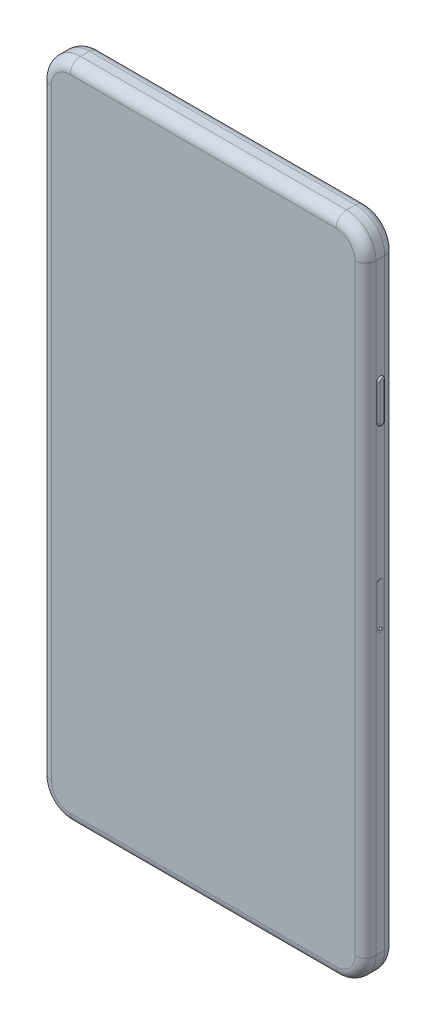
SolidWorks part; units mm, degrees
material "Cast Alloy Steel"
ref_plane "Front Plane" through (0, 0, 0) normal (0, 0, 1) x (1, 0, 0)
ref_plane "Top Plane" through (0, 0, 0) normal (0, 1, 0) x (1, 0, 0)
ref_plane "Right Plane" through (0, 0, 0) normal (1, 0, 0) x (0, 0, -1)
sketch "Sketch1" plane through (0, 0, 0) normal (0, 0, 1) x (1, 0, 0)
  line L0 (-36.2, 71.25) -> (-36.2, -71.25)
  line L1 (-31.7, 78.75) -> (31.7, 78.75)
  line L2 (-38.7, 71.75) -> (-38.7, -71.75)
  line L3 (-31.7, -78.75) -> (31.7, -78.75)
  line L4 (38.7, 71.75) -> (38.7, -71.75)
  line L5 (-38.7, 78.75) -> (38.7, -78.75) construction
  line L6 (-38.7, -78.75) -> (38.7, 78.75) construction
  line L7 (-31.2, -76.25) -> (31.2, -76.25)
  line L8 (36.2, 71.25) -> (36.2, -71.25)
  line L9 (-31.2, 76.25) -> (-22.375, 76.25)
  line L10 (-38.7, 78.75) -> (38.7, 78.75) construction
  line L11 (38.7, 78.75) -> (38.7, -78.75) construction
  line L12 (-38.7, 78.75) -> (-38.7, -78.75) construction
  line L13 (-38.7, -78.75) -> (38.7, -78.75) construction
  line L14 (36.2, 76.25) -> (36.2, -76.25) construction
  line L15 (-36.2, 76.25) -> (36.2, 76.25) construction
  line L16 (-36.2, -76.25) -> (36.2, -76.25) construction
  line L17 (-36.2, 76.25) -> (-36.2, -76.25) construction
  line L18 (22.375, 76.25) -> (31.2, 76.25)
  line L20 (-21.875, 75.75) -> (-21.875, 74.4325)
  line L21 (-18.875, 71.4325) -> (18.875, 71.4325)
  line L22 (21.875, 75.75) -> (21.875, 74.4325)
  arc A0 (31.7, 78.75) -> (38.7, 71.75) centre (31.7, 71.75) cw
  arc A1 (-38.7, -71.75) -> (-31.7, -78.75) centre (-31.7, -71.75) ccw
  arc A2 (-31.7, 78.75) -> (-38.7, 71.75) centre (-31.7, 71.75) ccw
  arc A3 (31.7, -78.75) -> (38.7, -71.75) centre (31.7, -71.75) ccw
  arc A4 (36.2, 71.25) -> (31.2, 76.25) centre (31.2, 71.25) ccw
  arc A5 (31.2, -76.25) -> (36.2, -71.25) centre (31.2, -71.25) ccw
  arc A6 (-36.2, -71.25) -> (-31.2, -76.25) centre (-31.2, -71.25) ccw
  arc A7 (-36.2, 71.25) -> (-31.2, 76.25) centre (-31.2, 71.25) cw
  arc A8 (18.875, 71.4325) -> (21.875, 74.4325) centre (18.875, 74.4325) ccw
  arc A9 (-21.875, 74.4325) -> (-18.875, 71.4325) centre (-18.875, 74.4325) ccw
  arc A10 (21.875, 75.75) -> (22.375, 76.25) centre (22.375, 75.75) cw
  arc A11 (-21.875, 75.75) -> (-22.375, 76.25) centre (-22.375, 75.75) ccw
  point P0 (0, 0)
  point P34 (0, 76.25)
  point P45 (21.875, 76.25)
  dimension "D4" = 7
  dimension "D5" = 5
  dimension "D6" = 3
  dimension "D7" = 0.5
  dimension "D1" = 157.5
  dimension "D2" = 77.4
  dimension "D3" = 2.5
extrude "Boss-Extrude1" add sketch "Sketch1" against normal blind 7.1 contours L2 A1 L3 A3 L4 A0 L1 A2
extrude "Cut-Extrude1" cut sketch "Sketch1<3>" against normal blind 0.1 contours L0 A6 L7 A5 L8 A4 L18 A10 L22 A8 L21 A9 L20 A11 L9 A7
sketch "Sketch1<3>" plane through (0, 0, 0) normal (0, 0, 1) x (1, 0, 0) same geometry as "Sketch1"
fillet "Fillet1" radius 2.5 16 edges at (-36.6497, 76.6997, 0) (0, 78.75, 0) (36.6497, 76.6997, 0) (38.7, 0, 0) (36.6497, -76.6997, 0) (0, -78.75, 0) (-36.6497, -76.6997, 0) (-38.7, 0, -7.1) (-36.6497, -76.6997, -7.1) (0, -78.75, -7.1) (36.6497, -76.6997, -7.1) (38.7, 0, -7.1) (36.6497, 76.6997, -7.1) (0, 78.75, -7.1) (-36.6497, 76.6997, -7.1) (-38.7, 0, 0)
sketch "Sketch2" plane through (0, 0, 0) normal (0, 0, 1) x (1, 0, 0)
  line L0 (0, 76.25) -> (0, 71.4325) construction
  line L1 (22.375, 76.25) -> (-22.375, 76.25) construction
  line L4 (-18.875, 71.4325) -> (18.875, 71.4325) construction
  line L5 (-4.3825, 73.8413) -> (4.3825, 73.8413) construction
  line L6 (-4.3825, 74.5173) -> (4.3825, 74.5173)
  line L7 (-4.3825, 73.1652) -> (4.3825, 73.1652)
  arc A3 (-4.3825, 74.5173) -> (-4.3825, 73.1652) centre (-4.3825, 73.8413) ccw
  arc A4 (4.3825, 73.1652) -> (4.3825, 74.5173) centre (4.3825, 73.8413) ccw
  circle A5 centre (7.3325, 73.8412) radius 0.676
  point P9 (0, 73.8412)
  dimension "D1" = 8.765
  dimension "D2" = 2.95
extrude "Cut-Extrude3" cut sketch "Sketch2" against normal blind 0.3
sketch "Sketch3" plane through (0, 0, -7.1) normal (0, 0, -1) x (-1, 0, 0)
  line L0 (-29.2, 69.25) -> (-29.2, 56.75) construction
  line L1 (-25.6, 69.25) -> (-25.6, 56.75)
  line L2 (-32.8, 69.25) -> (-32.8, 56.75)
  line L3 (31.7, 76.25) -> (-31.7, 76.25) construction
  line L4 (-36.2, 71.75) -> (-36.2, -71.75) construction
  arc A0 (-25.6, 69.25) -> (-32.8, 69.25) centre (-29.2, 69.25) ccw
  arc A1 (-32.8, 56.75) -> (-25.6, 56.75) centre (-29.2, 56.75) ccw
  circle A2 centre (-29.2, 63) radius 1.75
  circle A3 centre (-29.2, 69.25) radius 1.7
  circle A4 centre (-29.2, 56.75) radius 1.7
  point P2 (-29.2, 63)
  dimension "D4" = 3.6
  dimension "D1" = 12.5
  dimension "D2" = 7
  dimension "D3" = 7
sketch "Sketch4" plane through (38.7, 0, 0) normal (1, 0, 0) x (0, 0, -1)
  line L0 (2.5, 46.5699) -> (4.6, 46.5699) construction
  line L1 (2.5, 71.75) -> (2.5, -71.75) construction
  line L2 (4.6, -71.75) -> (4.6, 71.75) construction
  line L3 (3.55, 46.5699) -> (3.55, 38.0699) construction
  line L4 (4.3849, 46.5699) -> (4.3849, 38.0699)
  line L5 (2.7151, 46.5699) -> (2.7151, 38.0699)
  arc A0 (4.3849, 46.5699) -> (2.7151, 46.5699) centre (3.55, 46.5699) ccw
  arc A1 (2.7151, 38.0699) -> (4.3849, 38.0699) centre (3.55, 38.0699) ccw
  point P8 (3.55, 42.3199)
  point P13 (3.55, 43.1405)
  point P14 (3.55, 49.1617)
  point P15 (3.55, 42.3768)
  point P16 (3.55, 38.0699)
  dimension "D1" = 8.5
extrude "Boss-Extrude3" add sketch "Sketch4" along normal blind 0.4
fillet "Fillet3" radius 0.4 4 edges at (39.1, 42.3199, -4.3849) (39.1, 37.235, -3.55) (39.1, 42.3199, -2.7151) (39.1, 47.4049, -3.55)
sketch "Sketch5" plane through (38.7, 0, 0) normal (1, 0, 0) x (0, 0, -1)
  line L0 (2.5, 0) -> (4.6, 0) construction
  line L1 (2.5, 71.75) -> (2.5, -71.75) construction
  line L2 (4.6, -71.75) -> (4.6, 71.75) construction
  line L3 (3.55, -4.75) -> (3.55, 4.75) construction
  line L4 (2.7431, -4.75) -> (2.7431, 4.75)
  line L5 (4.3569, -4.75) -> (4.3569, 4.75)
  arc A0 (2.7431, -4.75) -> (4.3569, -4.75) centre (3.55, -4.75) ccw
  arc A1 (4.3569, 4.75) -> (2.7431, 4.75) centre (3.55, 4.75) ccw
  circle A2 centre (3.55, -4.75) radius 0.35
  point P8 (3.55, 0)
  dimension "D2" = 0.7
  dimension "D1" = 9.5
extrude "Boss-Extrude4" add sketch "Sketch5" along normal blind 0.02
sketch "Sketch6" plane through (38.7, 0, 0) normal (1, 0, 0) x (0, 0, -1)
  circle A0 centre (3.55, -4.75) radius 0.35
extrude "Cut-Extrude4" cut sketch "Sketch6" against normal blind 1
sketch "Sketch7" plane through (-38.7, 0, 0) normal (-1, 0, 0) x (0, 0, 1)
  line L0 (-2.7151, 46.5699) -> (-2.7151, 38.0699) construction
  line L1 (-4.3849, 38.0699) -> (-4.3849, 46.5699) construction
  line L2 (-2.7151, 46.5699) -> (-2.7151, 38.0699)
  line L3 (-4.3849, 38.0699) -> (-4.3849, 46.5699)
  line L4 (-4.6, 36.0651) -> (-2.5, 36.0651) construction
  line L5 (-4.6, 71.75) -> (-4.6, -71.75) construction
  line L6 (-2.5, -71.75) -> (-2.5, 71.75) construction
  line L7 (-4.3849, 34.0603) -> (-4.3849, 25.5603)
  line L8 (-2.7151, 25.5603) -> (-2.7151, 34.0603)
  arc A0 (-4.3849, 38.0699) -> (-2.7151, 38.0699) centre (-3.55, 38.0699) ccw construction
  arc A1 (-2.7151, 46.5699) -> (-4.3849, 46.5699) centre (-3.55, 46.5699) ccw construction
  arc A2 (-4.3849, 38.0699) -> (-2.7151, 38.0699) centre (-3.55, 38.0699) ccw
  arc A3 (-2.7151, 46.5699) -> (-4.3849, 46.5699) centre (-3.55, 46.5699) ccw
  arc A4 (-2.7151, 25.5603) -> (-4.3849, 25.5603) centre (-3.55, 25.5603) cw
  arc A5 (-4.3849, 34.0603) -> (-2.7151, 34.0603) centre (-3.55, 34.0603) cw
extrude "Boss-Extrude5" add sketch "Sketch7" along normal blind 0.4
fillet "Fillet4" radius 0.4 8 edges at (-39.1, 29.8103, -4.3849) (-39.1, 34.8952, -3.55) (-39.1, 29.8103, -2.7151) (-39.1, 24.7253, -3.55) (-39.1, 42.3199, -2.7151) (-39.1, 37.235, -3.55) (-39.1, 42.3199, -4.3849) (-39.1, 47.4049, -3.55)
sketch "Sketch8" plane through (-38.7, 0, 0) normal (-1, 0, 0) x (0, 0, 1)
  line L0 (-4.6, 52.4032) -> (-2.5, 52.4032) construction
  line L1 (-4.6, 71.75) -> (-4.6, -71.75) construction
  line L2 (-2.5, -71.75) -> (-2.5, 71.75) construction
  line L3 (-3.55, 50.6532) -> (-3.55, 54.1532) construction
  line L4 (-4.1722, 50.6532) -> (-4.1722, 54.1532)
  line L5 (-2.9278, 50.6532) -> (-2.9278, 54.1532)
  arc A0 (-4.1722, 50.6532) -> (-2.9278, 50.6532) centre (-3.55, 50.6532) ccw
  arc A1 (-2.9278, 54.1532) -> (-4.1722, 54.1532) centre (-3.55, 54.1532) ccw
  point P8 (-3.55, 52.4032)
  dimension "D1" = 3.5
extrude "Cut-Extrude5" cut sketch "Sketch8" against normal blind 0.3
sketch "Sketch10" plane through (0, -78.75, 0) normal (0, -1, 0) x (1, 0, 0)
  line L0 (0, 0) -> (0, -7.1) construction
  line L1 (31.7, -7.1) -> (-31.7, -7.1) construction
  line L2 (2.4161, -4.3017) -> (2.8576, -3.8603)
  line L3 (-2.6454, -2.769) -> (2.6454, -2.769)
  line L4 (-2.8869, -2.969) -> (-2.8869, -3.7896)
  line L5 (-2.3454, -4.331) -> (2.3454, -4.331)
  line L6 (2.8869, -2.969) -> (2.8869, -3.7896)
  line L7 (-2.8869, -2.769) -> (2.8869, -4.331) construction
  line L8 (-2.8869, -4.331) -> (2.8869, -2.769) construction
  line L9 (-2.8576, -3.8603) -> (-2.4161, -4.3017)
  line L10 (-2.8869, -2.969) -> (-2.7161, -2.7983)
  line L11 (2.7161, -2.7983) -> (2.8869, -2.969)
  line L12 (-31.7, -4.6) -> (-31.7, -2.5) construction
  arc A0 (2.7161, -2.7983) -> (2.6454, -2.769) centre (2.6454, -2.869) ccw
  arc A1 (-2.7161, -2.7983) -> (-2.6454, -2.769) centre (-2.6454, -2.869) cw
  arc A2 (-2.4161, -4.3017) -> (-2.3454, -4.331) centre (-2.3454, -4.231) ccw
  arc A3 (-2.8576, -3.8603) -> (-2.8869, -3.7896) centre (-2.7869, -3.7896) cw
  arc A4 (2.8576, -3.8603) -> (2.8869, -3.7896) centre (2.7869, -3.7896) ccw
  arc A5 (2.4161, -4.3017) -> (2.3454, -4.331) centre (2.3454, -4.231) cw
  circle A6 centre (4.9115, -3.5328) radius 0.5
  circle A7 centre (-4.9115, -3.5328) radius 0.5
  circle A8 centre (29.251, -3.5328) radius 0.62
  circle A9 centre (27.251, -3.5328) radius 0.62
  circle A10 centre (25.251, -3.5328) radius 0.62
  circle A11 centre (23.251, -3.5328) radius 0.62
  circle A12 centre (21.251, -3.5328) radius 0.62
  circle A13 centre (19.251, -3.5328) radius 0.62
  circle A14 centre (17.251, -3.5328) radius 0.62
  circle A15 centre (15.251, -3.5328) radius 0.62
  circle A16 centre (-26.7, -3.4998) radius 0.62
  circle A21 centre (-24.7, -3.4998) radius 0.62
  circle A22 centre (-22.7, -3.4998) radius 0.62
  circle A23 centre (-20.7, -3.4998) radius 0.62
  circle A24 centre (-18.7, -3.4998) radius 0.62
  point P5 (0, -3.55)
  point P20 (2.6869, -2.769)
  point P23 (-2.6869, -2.769)
  point P26 (-2.3869, -4.331)
  point P29 (-2.8869, -3.831)
  point P32 (2.8869, -3.831)
  point P35 (2.3869, -4.331)
  dimension "D1" = 0.1
  dimension "D2" = 1
  dimension "D7" = 1.24
  dimension "D9" = 5
  dimension "D8" = 8
  dimension "D10" = 5
extrude "Cut-Extrude6" cut sketch "Sketch10" against normal blind 1 contours A16 | A21 | A22 | A23 | A24 | A5 L2 A4 L6 L11 A0 L3 A1 L10 L4 A3 L9 A2 L5 | A14 | A13 | A12 | A10 | A8 | A9 | A15 | A11 region at (0, -78.75, -3.5357) region at (29.251, -78.75, -3.5328) region at (27.251, -78.75, -3.5328) region at (25.251, -78.75, -3.5328) region at (21.251, -78.75, -3.5328) region at (19.251, -78.75, -3.5328) region at (17.251, -78.75, -3.5328) region at (-26.7, -78.75, -3.4998) region at (-24.7, -78.75, -3.4998) region at (-22.7, -78.75, -3.4998) region at (-20.7, -78.75, -3.4998) region at (-18.7, -78.75, -3.4998)
extrude "Cut-Extrude7" cut sketch "Sketch10<3>" against normal blind 0.3 contours A6 | A7 region at (4.9115, -78.75, -3.5328)
sketch "Sketch10<3>" plane through (0, -78.75, 0) normal (0, -1, 0) x (1, 0, 0) same geometry as "Sketch10"
sketch "Sketch12" plane through (0, 0, -0.1) normal (0, 0, 1) x (1, 0, 0)
  line L0 (-31.2, -76.25) -> (31.2, -76.25) construction
  line L1 (36.2, 71.25) -> (36.2, -71.25) construction
  line L2 (22.375, 76.25) -> (31.2, 76.25) construction
  line L3 (-36.2, 71.25) -> (-36.2, -71.25) construction
  line L4 (-31.2, 76.25) -> (-22.375, 76.25) construction
  line L5 (22.375, 76.25) -> (-22.375, 76.25) construction
  line L6 (-31.2, -76.25) -> (31.2, -76.25)
  line L7 (36.2, 71.25) -> (36.2, -71.25)
  line L8 (22.375, 76.25) -> (31.2, 76.25)
  line L9 (-36.2, 71.25) -> (-36.2, -71.25)
  line L10 (-31.2, 76.25) -> (-22.375, 76.25)
  line L11 (22.375, 76.25) -> (-22.375, 76.25)
  arc A0 (-36.2, -71.25) -> (-31.2, -76.25) centre (-31.2, -71.25) ccw construction
  arc A1 (31.2, -76.25) -> (36.2, -71.25) centre (31.2, -71.25) ccw construction
  arc A2 (36.2, 71.25) -> (31.2, 76.25) centre (31.2, 71.25) ccw construction
  arc A3 (-31.7, 76.25) -> (-36.2, 71.75) centre (-31.7, 71.75) ccw construction
  arc A4 (-36.2, -71.25) -> (-31.2, -76.25) centre (-31.2, -71.25) ccw
  arc A5 (31.2, -76.25) -> (36.2, -71.25) centre (31.2, -71.25) ccw
  arc A6 (36.2, 71.25) -> (31.2, 76.25) centre (31.2, 71.25) ccw
  arc A7 (-31.7, 76.25) -> (-36.2, 71.75) centre (-31.7, 71.75) ccw
  arc M1 (-31.2, 76.25) -> (-36.2, 71.25) centre (-31.2, 71.25) ccw
  line M2 (-36.2, 71.25) -> (-36.2, -71.25)
  arc M3 (-36.2, -71.25) -> (-31.2, -76.25) centre (-31.2, -71.25) ccw
  line M4 (-31.2, -76.25) -> (31.2, -76.25)
  arc M5 (31.2, -76.25) -> (36.2, -71.25) centre (31.2, -71.25) ccw
  line M6 (36.2, -71.25) -> (36.2, 71.25)
  arc M7 (36.2, 71.25) -> (31.2, 76.25) centre (31.2, 71.25) ccw
  line M8 (31.2, 76.25) -> (22.375, 76.25)
  arc M9 (22.375, 76.25) -> (21.875, 75.75) centre (22.375, 75.75) ccw
  line M10 (21.875, 75.75) -> (21.875, 74.4325)
  arc M11 (21.875, 74.4325) -> (18.875, 71.4325) centre (18.875, 74.4325) cw
  line M12 (18.875, 71.4325) -> (-18.875, 71.4325)
  arc M13 (-18.875, 71.4325) -> (-21.875, 74.4325) centre (-18.875, 74.4325) cw
  line M14 (-21.875, 74.4325) -> (-21.875, 75.75)
  arc M15 (-21.875, 75.75) -> (-22.375, 76.25) centre (-22.375, 75.75) ccw
  line M16 (-22.375, 76.25) -> (-31.2, 76.25)
extrude "Boss-Extrude6" add sketch "Sketch12" along normal blind 0.1 contours M16 M1 M2 M3 M4 M5 M6 M7 M8 M9 M10 M11 M12 M13 M14 M15 | L11 M9 M15 M14 M13 M12 M11 M10 region at (0, -1.4144, -0.1) region at (0, 73.8749, -0.1)
